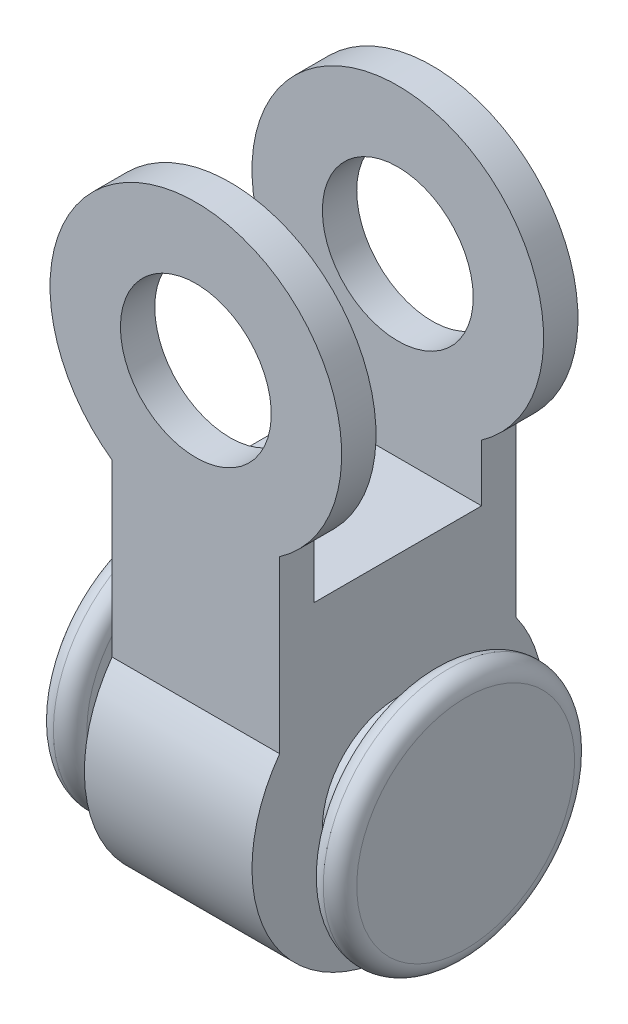
SolidWorks part; units mm, degrees
ref_plane "Front Plane" through (0, 0, 0) normal (0, 0, 1) x (1, 0, 0)
ref_plane "Top Plane" through (0, 0, 0) normal (0, 1, 0) x (1, 0, 0)
ref_plane "Right Plane" through (0, 0, 0) normal (1, 0, 0) x (0, 0, -1)
sketch "Sketch1" plane through (0, 0, 0) normal (1, 0, 0) x (0, 0, -1)
  circle A0 centre (0, 0) radius 87
  dimension "D1" = 174
extrude "Boss-Extrude3" add sketch "Sketch1" along normal blind 100
sketch "Sketch2" plane through (100, 0, 0) normal (1, 0, 0) x (0, 0, -1)
  circle A0 centre (0, 0) radius 45
  dimension "D1" = 90
extrude "Boss-Extrude4" add sketch "Sketch2" along normal blind 20.5
sketch "Sketch3" plane through (120.5, 0, 0) normal (1, 0, 0) x (0, 0, -1)
  circle A0 centre (0, 0) radius 75
  dimension "D1" = 150
extrude "Boss-Extrude5" add sketch "Sketch3" along normal blind 20
fillet "Fillet1" radius 10 2 edges at (120.5, 0, -75) (140.5, 0, -75)
sketch "Sketch4" plane through (0, 0, 0) normal (-1, 0, 0) x (0, 0, 1)
  circle A0 centre (0, 0) radius 45
  dimension "D1" = 90
extrude "Boss-Extrude6" add sketch "Sketch4" along normal blind 20.5
sketch "Sketch5" plane through (-20.5, 0, 0) normal (-1, 0, 0) x (0, 0, 1)
  circle A0 centre (0, 0) radius 75
  dimension "D1" = 150
extrude "Boss-Extrude7" add sketch "Sketch5" along normal blind 20
fillet "Fillet2" radius 10 2 edges at (-20.5, 0, 75) (-40.5, 0, 75)
ref_plane "Plane1" through (0, 87, 0) normal (0, 1, 0) x (1, 0, 0)
sketch "Sketch6" plane through (0, 87, 0) normal (0, 1, 0) x (1, 0, 0)
  line L0 (0, 87) -> (0, -87) construction
  line L1 (100, 70.5) -> (0, 70.5)
  line L2 (100, 70.5) -> (100, -70.5)
  line L3 (100, -70.5) -> (0, -70.5)
  line L4 (0, 70.5) -> (0, -70.5)
  line L5 (100, 70.5) -> (0, -70.5) construction
  line L6 (100, -70.5) -> (0, 70.5) construction
  point P0 (50, 0)
  point P5 (100, 0)
  dimension "D1" = 70.5
  dimension "D2" = 100
  dimension "D3" = 50
extrude "Boss-Extrude8" add sketch "Sketch6" against normal up to next
ref_plane "Plane4" through (0, 0, -70.5) normal (0, 0, -1) x (-1, 0, 0)
sketch "Sketch9" plane through (0, 0, -70.5) normal (0, 0, -1) x (-1, 0, 0)
  line L0 (-100, 87) -> (0, 87) construction
  line L2 (-100, 87) -> (0, 87)
  line L3 (-100, 87) -> (-100, 152.8031)
  line L5 (0, 87) -> (0, 152.8031)
  circle A1 centre (-50, 224) radius 45
  arc A2 (0, 152.8031) -> (-100, 152.8031) centre (-50, 224) ccw
  dimension "D4" = 90
  dimension "D6" = 174
  dimension "D1" = 137
  dimension "D2" = 100
extrude "Boss-Extrude10" add sketch "Sketch9" against normal blind 141
ref_plane "Plane7" through (100, 0, 0) normal (-1, 0, 0) x (0, 1, 0)
ref_plane "Plane8" through (147, 0, 0) normal (-1, 0, 0) x (0, 1, 0)
sketch "Sketch21" plane through (147, 0, 0) normal (-1, 0, 0) x (0, 1, 0)
  line L5 (87.9847, 70.5) -> (-87.9847, 70.5) construction
  line L6 (335.5696, 50) -> (118.8, 50)
  line L7 (335.5696, 50) -> (335.5696, -50)
  line L8 (335.5696, -50) -> (118.8, -50)
  line L9 (118.8, 50) -> (118.8, -50)
  line L10 (335.5696, 50) -> (118.8, -50) construction
  line L11 (335.5696, -50) -> (118.8, 50) construction
  line L13 (311, 70.5) -> (152.8031, 70.5) construction
  point P0 (227.1848, 0)
  dimension "D1" = 70.5
  dimension "D2" = 118.8
  dimension "D3" = 216.7696
  dimension "D4" = 20.5
extrude "Cut-Extrude2" cut sketch "Sketch21" along normal through all both and the other way through all contours L7 L6 L9 L8
